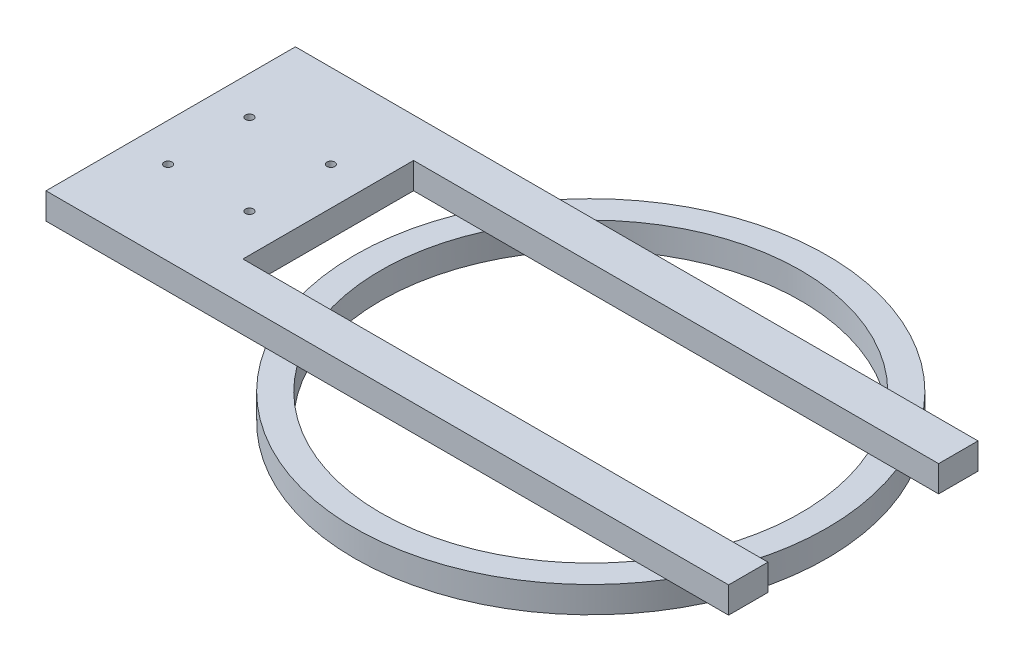
SolidWorks part; units mm, degrees
ref_plane "Front Plane" through (0, 0, 0) normal (0, 0, 1) x (1, 0, 0)
ref_plane "Top Plane" through (0, 0, 0) normal (0, 1, 0) x (1, 0, 0)
ref_plane "Right Plane" through (0, 0, 0) normal (1, 0, 0) x (0, 0, -1)
sketch "Sketch1" plane through (0, 0, 0) normal (0, 1, 0) x (1, 0, 0)
  circle A0 centre (0, 0) radius 90
  circle A1 centre (0, 0) radius 80
  dimension "D1" = 180
  dimension "D2" = 10
extrude "Boss-Extrude1" add sketch "Sketch1" along normal blind 10
sketch "Sketch2" plane through (0, 0, 0) normal (0, 0, 1) x (1, 0, 0)
  line L0 (0, 0) -> (-90, 0) construction
  line L1 (-90, 0) -> (90, 0) construction
  line L2 (0, 0) -> (0, 55.0975) construction
  circle A0 centre (-85, 0) radius 2.5
  dimension "D1" = 5
  dimension "D2" = 5
  dimension "D3" = 90
revolve "Cut-Revolve1" cut sketch "Sketch2" angle 360 about L2
sketch "Sketch3" plane through (0, 10, 0) normal (0, 1, 0) x (1, 0, 0)
  line L0 (-107.8637, 0) -> (120.1803, 0) construction
  line L1 (-100, -32.5) -> (100, -32.5)
  line L2 (-100, 47.5) -> (100, 47.5)
  line L3 (-100, 47.5) -> (-100, 32.5)
  line L4 (-100, 32.5) -> (100, 32.5)
  line L5 (100, 47.5) -> (100, 32.5)
  line L6 (-100, 47.5) -> (100, 32.5) construction
  line L7 (-100, 32.5) -> (100, 47.5) construction
  line L8 (100, -47.5) -> (100, -32.5)
  line L9 (-100, -47.5) -> (100, -47.5)
  line L10 (-100, -47.5) -> (-100, -32.5)
  point P3 (0, 40)
  point P12 (95.1018, 32.5)
  point P13 (0, 0)
  dimension "D1" = 200
  dimension "D2" = 40
  dimension "D3" = 15
extrude "Boss-Extrude2" add sketch "Sketch3" along normal blind 10
sketch "Sketch5" plane through (0, 10, 0) normal (0, -1, 0) x (1, 0, 0)
  line L0 (-100, 47.5) -> (-76.4444, 47.5) construction
  line L1 (-100, -47.5) -> (-160, -47.5)
  line L2 (-100, -47.5) -> (-100, 47.5)
  line L3 (-100, 47.5) -> (-160, 47.5)
  line L4 (-160, -47.5) -> (-160, 47.5)
  line L5 (-130, -69.1417) -> (-130, 74.349) construction
  line L6 (-176.3836, 0) -> (-91.62, 0) construction
  circle A0 centre (-145.5, -15.5) radius 1.5
  circle A1 centre (-114.5, -15.5) radius 1.5
  circle A2 centre (-114.5, 15.5) radius 1.5
  circle A3 centre (-145.5, 15.5) radius 1.5
  point P7 (-130, 47.5)
  point P8 (-130, -47.5)
  point P11 (-160, 0)
  point P12 (-100, 0)
  dimension "D4" = 3
  dimension "D1" = 60
  dimension "D2" = 31
  dimension "D3" = 31
extrude "Boss-Extrude3" add sketch "Sketch5" against normal blind 10
sketch "Sketch7" plane through (0, 10, 0) normal (0, -1, 0) x (1, 0, 0)
  line L0 (0, 0) -> (-130, 0) construction
  line L1 (-151.15, 21.15) -> (-108.85, 21.15)
  line L2 (-151.15, 21.15) -> (-151.15, -21.15)
  line L3 (-151.15, -21.15) -> (-108.85, -21.15)
  line L4 (-108.85, 21.15) -> (-108.85, -21.15)
  line L5 (-151.15, 21.15) -> (-108.85, -21.15) construction
  line L6 (-151.15, -21.15) -> (-108.85, 21.15) construction
  line L7 (-152.15, 22.15) -> (-152.15, -22.15)
  line L8 (-152.15, -22.15) -> (-107.85, -22.15)
  line L9 (-107.85, 22.15) -> (-107.85, -22.15)
  line L10 (-152.15, 22.15) -> (-107.85, 22.15)
  circle A0 centre (-145.5, 15.5) radius 1.5 construction
  circle A1 centre (-145.5, -15.5) radius 1.5 construction
  circle A2 centre (-114.5, -15.5) radius 1.5 construction
  circle A3 centre (-114.5, 15.5) radius 1.5 construction
  circle A4 centre (-145.5, -15.5) radius 1.5
  circle A5 centre (-114.5, -15.5) radius 1.5
  circle A6 centre (-114.5, 15.5) radius 1.5
  circle A7 centre (-145.5, 15.5) radius 1.5
  point P0 (-130, 0)
  dimension "D1" = 42.3
  dimension "D2" = 42.3
  dimension "D3" = 130
  dimension "D4" = 1
extrude "Boss-Extrude4" add sketch "Sketch7" along normal blind 5 contours L10 L7 L8 L9 L1 L4 L3 L2 region at (-130, 10, 21.5235)
